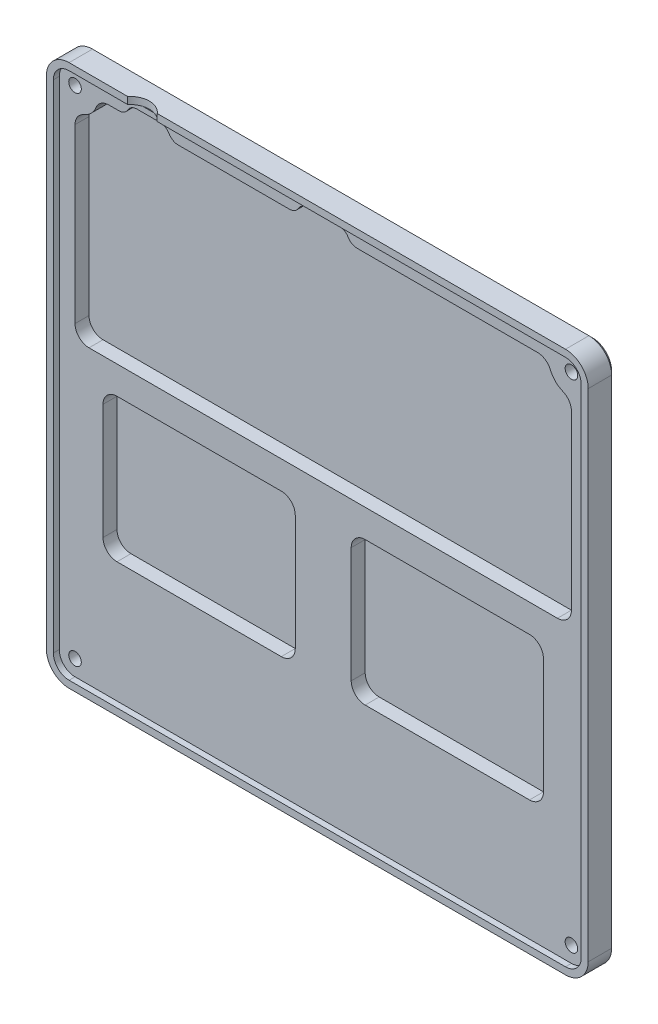
SolidWorks part; units mm, degrees
ref_plane "Front Plane" through (0, 0, 0) normal (0, 0, 1) x (1, 0, 0)
ref_plane "Top Plane" through (0, 0, 0) normal (0, 1, 0) x (1, 0, 0)
ref_plane "Right Plane" through (0, 0, 0) normal (1, 0, 0) x (0, 0, -1)
sketch "Sketch2" plane through (0, 0, 21.1137) normal (0, 0, -1) x (-1, 0, 0)
  line L0 (-26.4015, -76.7464) -> (-26.4015, 65.2536)
  line L1 (-25.9015, -80.7464) -> (124.0985, -80.7464) construction
  line L2 (-25.9015, -80.7464) -> (-25.9015, 69.2536) construction
  line L3 (-25.9015, 69.2536) -> (124.0985, 69.2536) construction
  line L4 (124.0985, -80.7464) -> (124.0985, 69.2536) construction
  line L5 (-21.9015, 69.7536) -> (120.0985, 69.7536)
  line L6 (124.5985, -76.7464) -> (124.5985, 65.2536)
  line L7 (-21.9015, -81.2464) -> (120.0985, -81.2464)
  line L8 (-28.4015, -76.7464) -> (-28.4015, 65.2536)
  line L9 (-21.9015, 71.7536) -> (120.0985, 71.7536)
  line L10 (126.5985, -76.7464) -> (126.5985, 65.2536)
  line L11 (-21.9015, -83.2464) -> (120.0985, -83.2464)
  line L15 (-26.4015, -81.2464) -> (-26.4015, 69.7536) construction
  line L16 (-26.4015, -81.2464) -> (124.5985, -81.2464) construction
  line L17 (-26.4015, 69.7536) -> (124.5985, 69.7536) construction
  line L18 (124.5985, -81.2464) -> (124.5985, 69.7536) construction
  line L19 (-28.4015, 71.7536) -> (126.5985, 71.7536) construction
  line L20 (126.5985, -83.2464) -> (126.5985, 71.7536) construction
  line L21 (-28.4015, -83.2464) -> (126.5985, -83.2464) construction
  line L22 (-28.4015, -83.2464) -> (-28.4015, 71.7536) construction
  line L23 (-21.9015, -80.7464) -> (120.0985, -80.7464) construction
  line L24 (124.0985, -76.7464) -> (124.0985, 65.2536) construction
  line L25 (120.0985, 69.2536) -> (-21.9015, 69.2536) construction
  arc A0 (-26.4015, -76.7464) -> (-21.9015, -81.2464) centre (-21.9015, -76.7464) ccw
  arc A1 (-26.4015, 65.2536) -> (-21.9015, 69.7536) centre (-21.9015, 65.2536) cw
  arc A2 (120.0985, 69.7536) -> (124.5985, 65.2536) centre (120.0985, 65.2536) cw
  arc A3 (124.5985, -76.7464) -> (120.0985, -81.2464) centre (120.0985, -76.7464) cw
  arc A4 (120.0985, 71.7536) -> (126.5985, 65.2536) centre (120.0985, 65.2536) cw
  arc A5 (126.5985, -76.7464) -> (120.0985, -83.2464) centre (120.0985, -76.7464) cw
  arc A6 (-28.4015, -76.7464) -> (-21.9015, -83.2464) centre (-21.9015, -76.7464) ccw
  arc A7 (-28.4015, 65.2536) -> (-21.9015, 71.7536) centre (-21.9015, 65.2536) cw
  dimension "D3" = 4.5
  dimension "D4" = 4.5
  dimension "D5" = 6.5
  dimension "D1" = 0.5
  dimension "D2" = 2
extrude "Boss-Extrude1" add sketch "Sketch2" against normal blind 1.7
sketch "Sketch4" plane through (0, 0, 21.1137) normal (0, 0, -1) x (-1, 0, 0)
  line L0 (-15.4015, 65.2536) -> (41.5985, 65.2536)
  line L4 (-28.4015, -76.7464) -> (-28.4015, 65.2536)
  line L6 (112.0985, -46.7464) -> (112.0985, -5.7464)
  line L8 (126.5985, -76.7464) -> (126.5985, 65.2536)
  line L11 (-21.9015, -83.2464) -> (120.0985, -83.2464)
  line L15 (112.0985, -46.7464) -> (57.0985, -46.7464)
  line L20 (41.0985, -46.7464) -> (41.0985, -5.7464)
  line L21 (120.0985, 2.2536) -> (-21.9015, 2.2536)
  line L23 (41.0985, -5.7464) -> (-13.9015, -5.7464)
  line L26 (41.5985, 68.2536) -> (56.5985, 68.2536)
  line L27 (56.5985, 68.2536) -> (56.5985, 65.2536)
  line L28 (56.5985, 65.2536) -> (92.7985, 65.2536)
  line L29 (92.7985, 65.2536) -> (92.7985, 68.2536)
  line L30 (92.7985, 68.2536) -> (105.3985, 68.2536)
  line L31 (105.3985, 68.2536) -> (105.3985, 65.2536)
  line L32 (105.3985, 65.2536) -> (113.5985, 65.2536)
  line L33 (120.0985, 71.7536) -> (-21.9015, 71.7536)
  line L34 (-13.9015, -46.7464) -> (-13.9015, -5.7464)
  line L35 (-15.4015, 65.2536) -> (41.5985, 65.2536) construction
  line L36 (-21.9015, 2.2536) -> (-21.9015, 58.7536)
  line L38 (41.5985, 65.2536) -> (41.5985, 68.2536)
  line L39 (120.0985, 69.7536) -> (-21.9015, 69.7536) construction
  line L40 (57.0985, -46.7464) -> (57.0985, -5.7464)
  line L41 (57.0985, -5.7464) -> (112.0985, -5.7464)
  line L45 (41.0985, -46.7464) -> (-13.9015, -46.7464)
  line L46 (120.0985, 2.2536) -> (120.0985, 58.7536)
  line L47 (41.0985, -5.7464) -> (57.0985, -5.7464) construction
  line L48 (-13.9015, -46.7464) -> (-28.4015, -46.7464) construction
  line L49 (112.0985, -46.7464) -> (126.5985, -46.7464) construction
  arc A0 (-21.9015, 71.7536) -> (-28.4015, 65.2536) centre (-21.9015, 65.2536) ccw
  arc A2 (-21.9015, 71.7536) -> (-28.4015, 65.2536) centre (-21.9015, 65.2536) ccw construction
  arc A3 (-28.4015, -76.7464) -> (-21.9015, -83.2464) centre (-21.9015, -76.7464) ccw
  arc A4 (120.0985, -83.2464) -> (126.5985, -76.7464) centre (120.0985, -76.7464) ccw
  arc A5 (126.5985, 65.2536) -> (120.0985, 71.7536) centre (120.0985, 65.2536) ccw
  arc A6 (126.5985, 65.2536) -> (120.0985, 71.7536) centre (120.0985, 65.2536) ccw construction
  arc A7 (120.0985, -83.2464) -> (126.5985, -76.7464) centre (120.0985, -76.7464) ccw construction
  arc A8 (-28.4015, -76.7464) -> (-21.9015, -83.2464) centre (-21.9015, -76.7464) ccw construction
  arc A11 (-21.9015, 58.7536) -> (-15.4015, 65.2536) centre (-21.9015, 65.2536) ccw
  arc A12 (126.5985, 65.2536) -> (120.0985, 71.7536) centre (120.0985, 65.2536) ccw
  arc A13 (113.5985, 65.2536) -> (120.0985, 58.7536) centre (120.0985, 65.2536) ccw
  arc A14 (103.3485, 64.6286) -> (102.4485, 64.6286) centre (102.8985, 64.6286) ccw construction
  arc A15 (95.7485, 64.6286) -> (94.8485, 64.6286) centre (95.2985, 64.6286) ccw construction
  point P19 (84.5985, -5.7464)
  line M1 (120.0985, -81.2464) -> (-21.9015, -81.2464)
  arc M2 (-21.9015, -81.2464) -> (-26.4015, -76.7464) centre (-21.9015, -76.7464) cw
  line M3 (-26.4015, -76.7464) -> (-26.4015, 65.2536)
  arc M4 (-26.4015, 65.2536) -> (-21.9015, 69.7536) centre (-21.9015, 65.2536) cw
  line M5 (-21.9015, 69.7536) -> (120.0985, 69.7536)
  arc M6 (120.0985, 69.7536) -> (124.5985, 65.2536) centre (120.0985, 65.2536) cw
  line M7 (124.5985, 65.2536) -> (124.5985, -76.7464)
  arc M8 (124.5985, -76.7464) -> (120.0985, -81.2464) centre (120.0985, -76.7464) cw
  arc M9 (126.5985, 65.2536) -> (120.0985, 71.7536) centre (120.0985, 65.2536) ccw
  line M10 (120.0985, 71.7536) -> (-21.9015, 71.7536)
  arc M11 (-21.9015, 71.7536) -> (-28.4015, 65.2536) centre (-21.9015, 65.2536) ccw
  line M12 (-28.4015, 65.2536) -> (-28.4015, -76.7464)
  arc M13 (-28.4015, -76.7464) -> (-21.9015, -83.2464) centre (-21.9015, -76.7464) ccw
  line M14 (-21.9015, -83.2464) -> (120.0985, -83.2464)
  arc M15 (120.0985, -83.2464) -> (126.5985, -76.7464) centre (120.0985, -76.7464) ccw
  line M16 (126.5985, -76.7464) -> (126.5985, 65.2536)
  dimension "D7" = 2.5
  dimension "D8" = 2.5
  dimension "D1" = 55
  dimension "D2" = 16
  dimension "D3" = 8
  dimension "D4" = 8
  dimension "D5" = 1.5
  dimension "D6" = 6.5
  dimension "D9" = 6.5
  dimension "D10" = 56.5
  dimension "D11" = 41
  dimension "D12" = 70
  dimension "D13" = 70
extrude "Boss-Extrude2" add sketch "Sketch4" along normal blind 4 contours M16 M9 M10 M11 M12 M13 M14 M15 M8 M1 M2 M3 M4 M5 M6 M7 | L40 L41 L6 L15 L20 L45 L34 L23 L32 A13 L46 L21 L36 A11 L0 L38 L26 L27 L28 L29 L30 L31 M1 M8 M7 M6 M5 M4 M3 M2 region at (28.1823, -5.7464, 21.1137) region at (-48.8955, -33.926, 21.1137)
fillet "Fillet1" radius 4 14 edges at (-112.0985, -46.7464, 19.1137) (-112.0985, -5.7464, 19.1137) (-57.0985, -5.7464, 19.1137) (-57.0985, -46.7464, 19.1137) (-41.0985, -46.7464, 19.1137) (13.9015, -46.7464, 19.1137) (13.9015, -5.7464, 19.1137) (-41.0985, -5.7464, 19.1137) (21.9015, 58.7536, 19.1137) (15.4015, 65.2536, 19.1137) (-120.0985, 2.2536, 19.1137) (21.9015, 2.2536, 19.1137) (-120.0985, 58.7536, 19.1137) (-113.5985, 65.2536, 19.1137)
fillet "Fillet2" radius 3 4 edges at (-92.7985, 68.2536, 19.1137) (-105.3985, 68.2536, 19.1137) (-41.5985, 68.2536, 19.1137) (-56.5985, 68.2536, 19.1137)
fillet "Fillet3" radius 3 4 edges at (-41.5985, 65.2536, 19.1137) (-56.5985, 65.2536, 19.1137) (-105.3985, 65.2536, 19.1137) (-92.7985, 65.2536, 19.1137)
sketch "Sketch8" plane through (0, 0, 17.1137) normal (0, 0, -1) x (-1, 0, 0)
  line L8 (-21.9015, -83.2464) -> (120.0985, -83.2464) construction
  line L9 (126.5985, -76.7464) -> (126.5985, 65.2536) construction
  line L10 (120.0985, 71.7536) -> (-21.9015, 71.7536) construction
  line L11 (-28.4015, 65.2536) -> (-28.4015, -76.7464) construction
  line L12 (-21.9015, -83.2464) -> (120.0985, -83.2464)
  line L13 (126.5985, -76.7464) -> (126.5985, 65.2536)
  line L14 (120.0985, 71.7536) -> (-21.9015, 71.7536)
  line L15 (-28.4015, 65.2536) -> (-28.4015, -76.7464)
  arc A8 (-28.4015, -76.7464) -> (-21.9015, -83.2464) centre (-21.9015, -76.7464) ccw construction
  arc A9 (120.0985, -83.2464) -> (126.5985, -76.7464) centre (120.0985, -76.7464) ccw construction
  arc A10 (126.5985, 65.2536) -> (120.0985, 71.7536) centre (120.0985, 65.2536) ccw construction
  arc A11 (-21.9015, 71.7536) -> (-28.4015, 65.2536) centre (-21.9015, 65.2536) ccw construction
  arc A12 (-28.4015, -76.7464) -> (-21.9015, -83.2464) centre (-21.9015, -76.7464) ccw
  arc A13 (120.0985, -83.2464) -> (126.5985, -76.7464) centre (120.0985, -76.7464) ccw
  arc A14 (126.5985, 65.2536) -> (120.0985, 71.7536) centre (120.0985, 65.2536) ccw
  arc A15 (-21.9015, 71.7536) -> (-28.4015, 65.2536) centre (-21.9015, 65.2536) ccw
extrude "Boss-Extrude3" add sketch "Sketch8" along normal blind 2
sketch "Sketch9" plane through (0, 71.7536, 0) normal (0, 1, 0) x (1, 0, 0)
  circle A0 centre (-99.0985, -26.3795) radius 5.525
  arc A3 (-94.2735, -26.3795) -> (-103.9235, -26.3795) centre (-99.0985, -26.3795) ccw construction
  arc A4 (-101.4085, -26.3795) -> (-96.7885, -26.3795) centre (-99.0985, -26.3795) ccw construction
  dimension "D1" = 0.7
extrude "Cut-Extrude1" cut sketch "Sketch9" against normal up to surface (2 mm away) up to face at (-49.0985, 69.7536, 21.9637)
chamfer "Chamfer1" distance 1 angle 45 8 edges at (28.4015, -5.7464, 15.1137) (26.4977, 69.8498, 15.1137) (-49.0985, 71.7536, 15.1137) (-124.6947, 69.8498, 15.1137) (-126.5985, -5.7464, 15.1137) (-124.6947, -81.3426, 15.1137) (-49.0985, -83.2464, 15.1137) (26.4977, -81.3426, 15.1137)
sketch "Sketch11" plane through (0, 0, 15.1137) normal (0, 0, -1) x (-1, 0, 0)
  point P0 (-21.9015, -76.7464)
  point P1 (-21.9015, 65.2536)
  point P3 (120.0985, 65.2536)
  point P5 (120.0985, -76.7464)
hole_wizard "CSK for M3 Flat Head Machine Screw2" positions "Sketch14" profile "Sketch13" countersink size "M3" standard "ANSI Metric" end condition through all
sketch "Sketch14" plane through (0, 0, 15.1137) normal (0, 0, -1) x (-1, 0, 0)
  point P0 (-21.9015, 65.2536)
  point P3 (120.0985, 65.2536)
  point P6 (120.0985, -76.7464)
  point P9 (-21.9015, -76.7464)
sketch "Sketch13" plane through (21.9015, 65.2536, 15.1137) normal (1, 0, 0) x (0, 1, 0)
  line L0 (0, 0) -> (0, 7.7)
  line L1 (0, 7.7) -> (1.8, 7.7)
  line L2 (1.8, 7.7) -> (1.8, 1.55)
  line L3 (1.8, 1.55) -> (3.35, 0)
  line L5 (3.35, 0) -> (0, 0)
  line L6 (-1.8, 1.55) -> (-3.35, 0) construction
  line L11 (0, -6.35) -> (0, 107.95) construction
  dimension "Thru Hole Dia." = 3.6
  dimension "Thru Hole Depth" = 7.7
  dimension "Near C'Sink Dia." = 6.7
  dimension "Near C'Sink Angle" = 90
